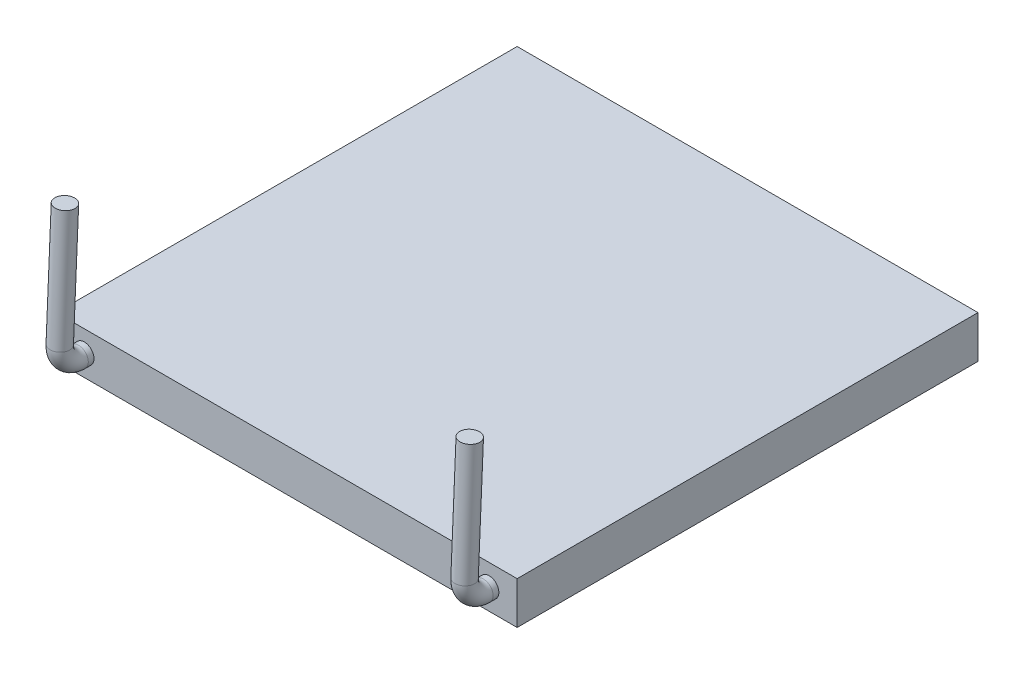
SolidWorks part; units mm, degrees
ref_plane "Front Plane" through (0, 0, 0) normal (0, 0, 1) x (1, 0, 0)
ref_plane "Top Plane" through (0, 0, 0) normal (0, 1, 0) x (1, 0, 0)
ref_plane "Right Plane" through (0, 0, 0) normal (1, 0, 0) x (0, 0, -1)
sketch "Sketch1" plane through (0, 0, 0) normal (0, 1, 0) x (1, 0, 0)
  line L1 (-20.15, 20.15) -> (20.15, 20.15)
  line L2 (-20.15, 20.15) -> (-20.15, -20.15)
  line L3 (-20.15, -20.15) -> (20.15, -20.15)
  line L4 (20.15, 20.15) -> (20.15, -20.15)
  line L5 (-20.15, 20.15) -> (20.15, -20.15) construction
  line L6 (-20.15, -20.15) -> (20.15, 20.15) construction
  point P0 (0, 0)
  dimension "D1" = 40.3
extrude "Boss-Extrude1" add sketch "Sketch1" along normal blind 3.7
sketch "Sketch3" plane through (0, 0, 20.15) normal (0, 0, 1) x (1, 0, 0)
  line L0 (-20.15, 1.85) -> (20.15, 1.85) construction
  line L1 (-20.15, 3.7) -> (-20.15, 0) construction
  line L2 (20.15, 3.7) -> (20.15, 0) construction
  line L3 (-20.15, 3.7) -> (-17.7, 1.85) construction
  circle A0 centre (-17.7, 1.85) radius 0.85
  dimension "D2" = 1.7
  dimension "D1" = 2.45
extrude "Boss-Extrude2" add sketch "Sketch3" along normal blind 0.5 contours A0
ref_point "Point1"
ref_plane "Plane1" through (-17.7, 0, 0) normal (-1, 0, 0) x (0, 0, 1)
sketch "Sketch5" plane through (0, 0, 20.65) normal (0, 0, 1) x (1, 0, 0)
  circle A1 centre (-17.7, 1.85) radius 0.85
  circle A2 centre (-17.7, 1.85) radius 0.85
  dimension "D1" = 0
sketch "Sketch4" plane through (-17.7, 0, 0) normal (-1, 0, 0) x (0, 0, 1)
  line L0 (20.65, 1) -> (20.65, 2.7) construction
  line L2 (20.65, 1.85) -> (20.65, 5.4991) construction
  line L3 (20.65, 1.85) -> (20.65, 1) construction
  line L4 (22.3, 3.5734) -> (23.15, 3.5734) construction
  line L5 (20.15, 3.7) -> (20.15, 0) construction
  arc A0 (20.65, 1.85) -> (22.3, 3.5734) centre (20.65, 3.5016) ccw
  dimension "D1" = 3
sweep "Sweep1" add profiles "Sketch5" path "Sketch4"
sketch "Sketch6" plane through (0, 2.5977, -0.1131) normal (0, 0.9991, -0.0435) x (1, 0, 0)
  circle A1 centre (-17.7, -22.4343) radius 0.85
  circle A2 centre (-17.7, -22.4343) radius 0.85
  dimension "D1" = 0
extrude "Boss-Extrude3" add sketch "Sketch6" along normal blind 10.5
mirror "Mirror1" about plane through (0, 0, 0) normal (1, 0, 0) of "Boss-Extrude2", "Sweep1", "Boss-Extrude3"
